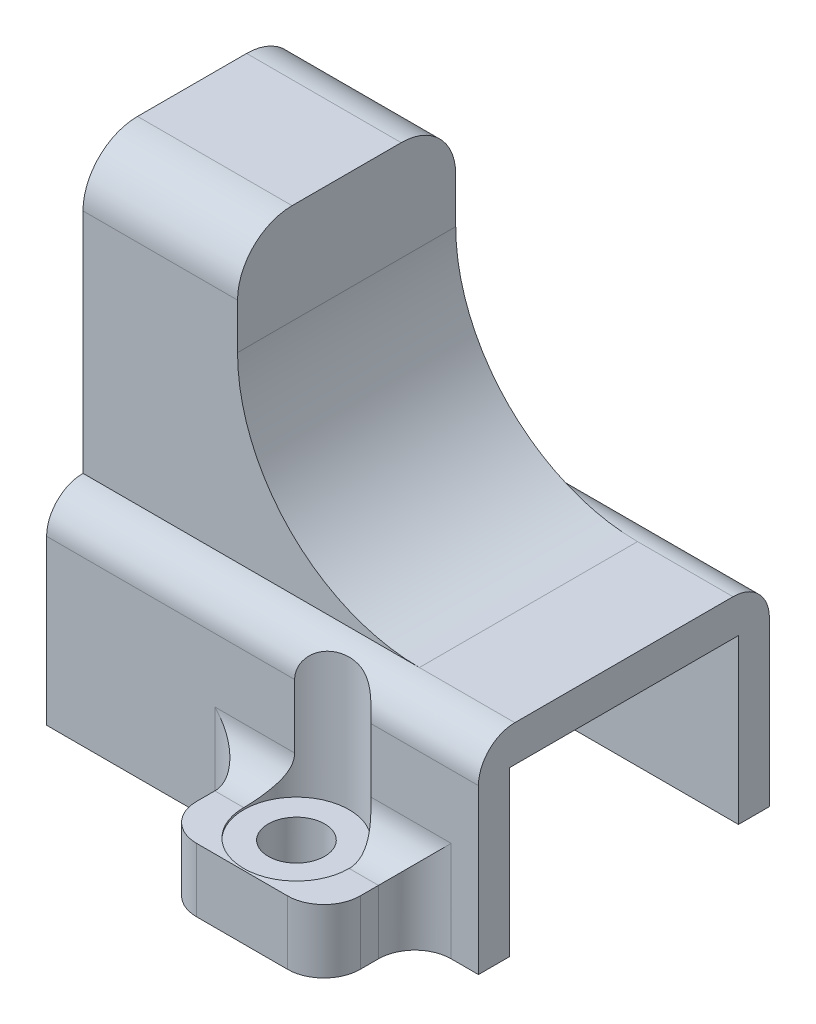
SolidWorks part; units mm, degrees
ref_plane "Alzado" through (0, 0, 0) normal (0, 0, 1) x (1, 0, 0)
ref_plane "Planta" through (0, 0, 0) normal (0, 1, 0) x (1, 0, 0)
ref_plane "Vista lateral" through (0, 0, 0) normal (1, 0, 0) x (0, 0, -1)
sketch "Croquis1" plane through (0, 0, 0) normal (0, 1, 0) x (1, 0, 0)
  line L1 (0, 0) -> (18.75, 0)
  line L2 (0, 0) -> (0, 16)
  line L3 (0, 16) -> (18.75, 16)
  line L4 (18.75, 0) -> (18.75, 16)
  dimension "D1" = 18.75
  dimension "D2" = 16
extrude "Saliente-Extruir1" add sketch "Croquis1" along normal blind 10
sketch "Croquis2" plane through (0, 0, 0) normal (0, -1, 0) x (1, 0, 0)
  line L19 (18.75, 0) -> (18.75, -16) construction
  line L20 (0, -16) -> (0, 0) construction
  line L22 (0, 0) -> (18.75, 0) construction
  line L23 (0, -1.7) -> (18.75, -1.7)
  line L24 (0, -1.7) -> (0, -14.3)
  line L25 (0, -14.3) -> (18.75, -14.3)
  line L26 (18.75, -1.7) -> (18.75, -14.3)
  line L27 (18.75, -16) -> (0, -16) construction
  point P10 (9.375, 0)
  dimension "D1" = 1.7
  dimension "D2" = 1.7
extrude "Cortar-Extruir1" cut sketch "Croquis2" against normal blind 8
sketch "Croquis3" plane through (0, 0, 0) normal (0, 0, 1) x (1, 0, 0)
  line L0 (0, 0) -> (18.75, 0) construction
  line L1 (6.25, 0) -> (15.25, 0)
  line L2 (6.25, 0) -> (6.25, 2.5)
  line L3 (6.25, 2.5) -> (15.25, 2.5)
  line L4 (15.25, 0) -> (15.25, 2.5)
  line L5 (18.75, 10) -> (18.75, 0) construction
  dimension "D1" = 2.5
  dimension "D2" = 3.5
  dimension "D3" = 9
extrude "Saliente-Extruir2" add sketch "Croquis3" along normal blind 5
sketch "Croquis4" plane through (0, 2.5, 0) normal (0, 1, 0) x (1, 0, 0)
  line L0 (18.75, 0) -> (18.75, 16) construction
  line L1 (15.25, 0) -> (6.25, 0) construction
  circle A0 centre (10.74, -2) radius 1.55
  dimension "D1" = 3.1
  dimension "D2" = 8.01
  dimension "D3" = 2
extrude "Cortar-Extruir2" cut sketch "Croquis4" against normal up to surface (2.5 mm away) up to face at (9.375, 0, -15.15)
fillet "Redondeo1" radius 2 7 edges at (9.375, 10, -16) (9.375, 10, 0) (6.25, 1.25, 5) (15.25, 1.25, 5) (10.75, 2.5, 0) (15.25, 1.25, 0) (6.25, 1.25, 0)
sketch "Croquis5" plane through (0, 10, 0) normal (0, 1, 0) x (1, 0, 0)
  circle A0 centre (10.74, -2) radius 2.9
  dimension "D1" = 5.8
extrude "Cortar-Extruir3" cut sketch "Croquis5" against normal blind 7.6
sketch "Croquis6" plane through (0, 10, 0) normal (0, 1, 0) x (1, 0, 0)
  line L0 (0, 2) -> (18.75, 2) construction
  line L1 (0, 14) -> (3.5, 14)
  line L2 (0, 14) -> (0, 2)
  line L3 (0, 2) -> (3.5, 2)
  line L4 (3.5, 14) -> (3.5, 2)
  dimension "D1" = 3.5
extrude "Saliente-Extruir3" add sketch "Croquis6" along normal blind 15.5
fillet "Redondeo2" radius 10 1 edges at (3.5, 10, -8)
fillet "Redondeo3" radius 3 2 edges at (1.75, 25.5, -14) (1.75, 25.5, -2)
sketch "Croquis7" plane through (0, 0, 0) normal (-1, 0, 0) x (0, 0, 1)
  line L0 (-14.3, 0) -> (-14.3, 8)
  line L1 (-14.3, 8) -> (-1.7, 8)
  line L2 (-1.7, 8) -> (-1.7, 0)
  line L10 (-5, 25.5) -> (-11, 25.5)
  line L11 (-14, 22.5) -> (-14, 10)
  line L12 (-16, 8) -> (-16, 0)
  line L13 (-16, 0) -> (-14.3, 0)
  line L14 (-14.3, 0) -> (-14.3, 8)
  line L15 (-14.3, 8) -> (-1.7, 8)
  line L16 (-1.7, 8) -> (-1.7, 0)
  line L17 (-1.7, 0) -> (0, 0)
  line L18 (0, 0) -> (0, 8)
  line L19 (-2, 10) -> (-2, 22.5)
  line L20 (-5, 25.5) -> (-11, 25.5)
  line L21 (-14, 22.5) -> (-14, 10)
  line L22 (-16, 8) -> (-16, 0)
  line L23 (-16, 0) -> (-14.3, 0)
  line L27 (-1.7, 0) -> (0, 0)
  line L28 (0, 0) -> (0, 8)
  line L29 (-2, 10) -> (-2, 22.5)
  arc A4 (-11, 25.5) -> (-14, 22.5) centre (-11, 22.5) ccw
  arc A5 (-14, 10) -> (-16, 8) centre (-14, 8) ccw
  arc A6 (0, 8) -> (-2, 10) centre (-2, 8) ccw
  arc A7 (-2, 22.5) -> (-5, 25.5) centre (-5, 22.5) ccw
  arc A8 (-11, 25.5) -> (-14, 22.5) centre (-11, 22.5) ccw
  arc A9 (-14, 10) -> (-16, 8) centre (-14, 8) ccw
  arc A10 (0, 8) -> (-2, 10) centre (-2, 8) ccw
  arc A11 (-2, 22.5) -> (-5, 25.5) centre (-5, 22.5) ccw
  dimension "D1" = 0
extrude "Saliente-Extruir4" add sketch "Croquis7" along normal blind 5
sketch "Croquis8" plane through (0, 0, 0) normal (0, -1, 0) x (1, 0, 0)
  line L4 (18.75, -14.3) -> (-5, -14.3)
  line L5 (-5, -14.3) -> (-5, -16)
  line L6 (-5, -16) -> (18.75, -16)
  line L7 (18.75, -16) -> (18.75, -14.3)
  line L8 (13.25, 5) -> (8.25, 5)
  line L9 (6.25, 3) -> (6.25, 2)
  line L10 (4.25, 0) -> (-5, 0)
  line L11 (-5, 0) -> (-5, -1.7)
  line L12 (-5, -1.7) -> (18.75, -1.7)
  line L13 (18.75, -1.7) -> (18.75, 0)
  line L14 (18.75, 0) -> (17.25, 0)
  line L15 (15.25, 2) -> (15.25, 3)
  line L16 (13.25, 5) -> (8.25, 5)
  line L17 (6.25, 3) -> (6.25, 2)
  line L18 (4.25, 0) -> (-5, 0)
  line L19 (-5, 0) -> (-5, -1.7)
  line L20 (-5, -1.7) -> (18.75, -1.7)
  line L21 (18.75, -1.7) -> (18.75, 0)
  line L22 (18.75, 0) -> (17.25, 0)
  line L23 (15.25, 2) -> (15.25, 3)
  line L24 (18.75, -14.3) -> (-5, -14.3)
  line L25 (-5, -14.3) -> (-5, -16)
  line L26 (-5, -16) -> (18.75, -16)
  line L27 (18.75, -16) -> (18.75, -14.3)
  circle A0 centre (10.74, 2) radius 1.55 construction
  circle A1 centre (10.74, 2) radius 1.55
  arc A4 (8.25, 5) -> (6.25, 3) centre (8.25, 3) ccw
  arc A5 (4.25, 0) -> (6.25, 2) centre (4.25, 2) ccw
  arc A6 (15.25, 2) -> (17.25, 0) centre (17.25, 2) ccw
  arc A7 (15.25, 3) -> (13.25, 5) centre (13.25, 3) ccw
  arc A8 (8.25, 5) -> (6.25, 3) centre (8.25, 3) ccw
  arc A9 (4.25, 0) -> (6.25, 2) centre (4.25, 2) ccw
  arc A10 (15.25, 2) -> (17.25, 0) centre (17.25, 2) ccw
  arc A11 (15.25, 3) -> (13.25, 5) centre (13.25, 3) ccw
  dimension "D1" = 0
  dimension "D2" = 0
extrude "Saliente-Extruir5" add sketch "Croquis8" along normal blind 1
